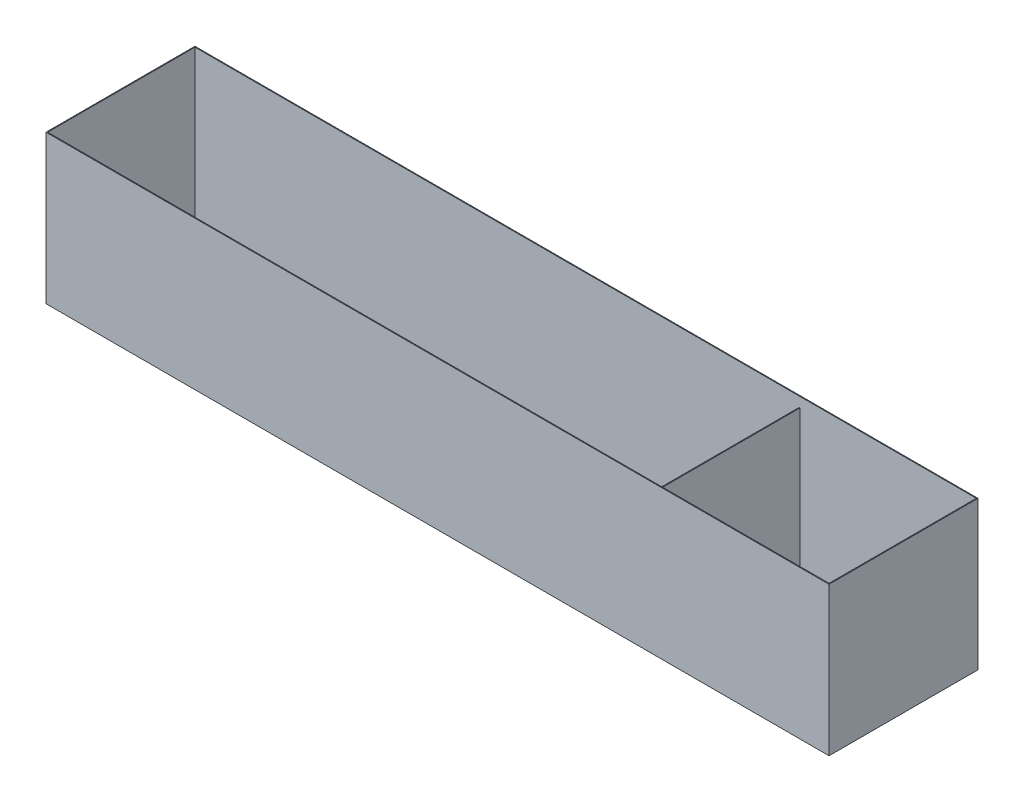
SolidWorks part; units mm, degrees
ref_plane "Front Plane" through (0, 0, 0) normal (0, 0, 1) x (1, 0, 0)
ref_plane "Top Plane" through (0, 0, 0) normal (0, 1, 0) x (1, 0, 0)
ref_plane "Right Plane" through (0, 0, 0) normal (1, 0, 0) x (0, 0, -1)
sketch "Sketch1" plane through (0, 0, 0) normal (0, 1, 0) x (1, 0, 0)
  line L141 (11988.8, 38.1) -> (11988.8, 2311.4)
  line L142 (38.1, 38.1) -> (11988.8, 38.1)
  line L143 (38.1, 2311.4) -> (38.1, 38.1)
  line L144 (11988.8, 2311.4) -> (38.1, 2311.4)
  line L145 (11988.8, 38.1) -> (11988.8, 2311.4)
  line L146 (38.1, 38.1) -> (11988.8, 38.1)
  line L147 (38.1, 2311.4) -> (38.1, 38.1)
  line L148 (11988.8, 2311.4) -> (38.1, 2311.4)
  line L153 (50.8, 2298.7) -> (50.8, 50.8)
  line L154 (50.8, 50.8) -> (11976.1, 50.8)
  line L155 (11976.1, 50.8) -> (11976.1, 2298.7)
  line L156 (11976.1, 2298.7) -> (50.8, 2298.7)
  line L157 (50.8, 2298.7) -> (50.8, 50.8)
  line L158 (50.8, 50.8) -> (11976.1, 50.8)
  line L159 (11976.1, 50.8) -> (11976.1, 2298.7)
  line L160 (11976.1, 2298.7) -> (50.8, 2298.7)
  line L165 (9436.1, 50.8) -> (9436.1, 2146.3)
  line L166 (9423.4, 50.8) -> (9436.1, 50.8)
  line L167 (9423.4, 2146.3) -> (9423.4, 50.8)
  line L168 (9436.1, 2146.3) -> (9423.4, 2146.3)
  line L169 (9436.1, 50.8) -> (9436.1, 2146.3)
  line L170 (9423.4, 50.8) -> (9436.1, 50.8)
  line L171 (9423.4, 2146.3) -> (9423.4, 50.8)
  line L172 (9436.1, 2146.3) -> (9423.4, 2146.3)
  dimension "D1" = 0
  dimension "D2" = 0
  dimension "D3" = 0
extrude "Boss-Extrude1" add sketch "Sketch1" along normal up to surface (2266.95 mm away) contours L145 L148 L147 L146 L160 L159 L158 L157 | L169 L172 L171 L158 region at (6013.45, 0, -50.265) region at (9429.75, 0, -1098.55)
